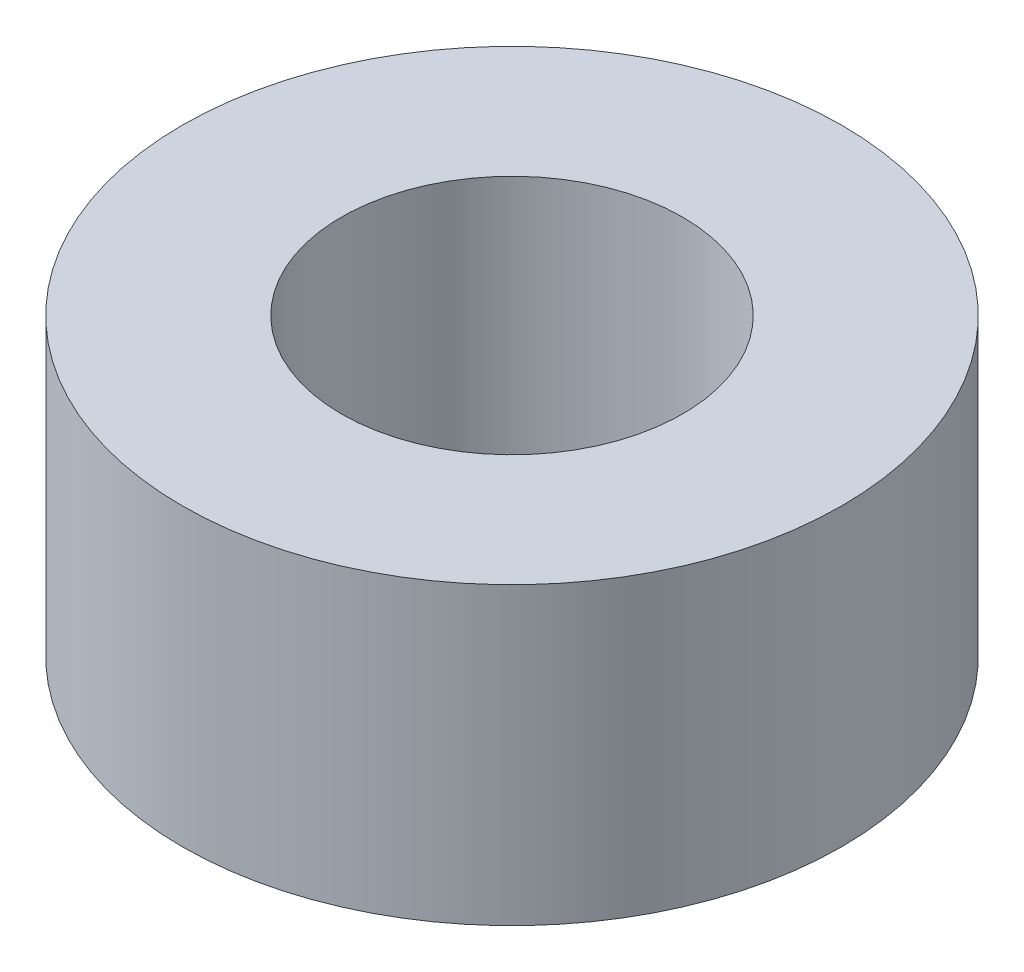
SolidWorks part; units mm, degrees
ref_plane "Front Plane" through (0, 0, 0) normal (0, 0, 1) x (1, 0, 0)
ref_plane "Top Plane" through (0, 0, 0) normal (0, 1, 0) x (1, 0, 0)
ref_plane "Right Plane" through (0, 0, 0) normal (1, 0, 0) x (0, 0, -1)
sketch "Sketch1" plane through (0, 0, 0) normal (0, 1, 0) x (1, 0, 0)
  circle A0 centre (0, 0) radius 10
  dimension "SLEEVE_OD" = 20
extrude "Boss-Extrude1" add sketch "Sketch1" along normal blind 8.9559
sketch "Sketch2" plane through (0, 0, 0) normal (0, 1, 0) x (1, 0, 0)
  circle A0 centre (0, 0) radius 5.174
  dimension "BORE_D" = 10.3479
extrude "Cut-Extrude1" cut sketch "Sketch2" along normal through all
chamfer "Chamfer1" distance 1.8492 angle 60 rebuild error yes
